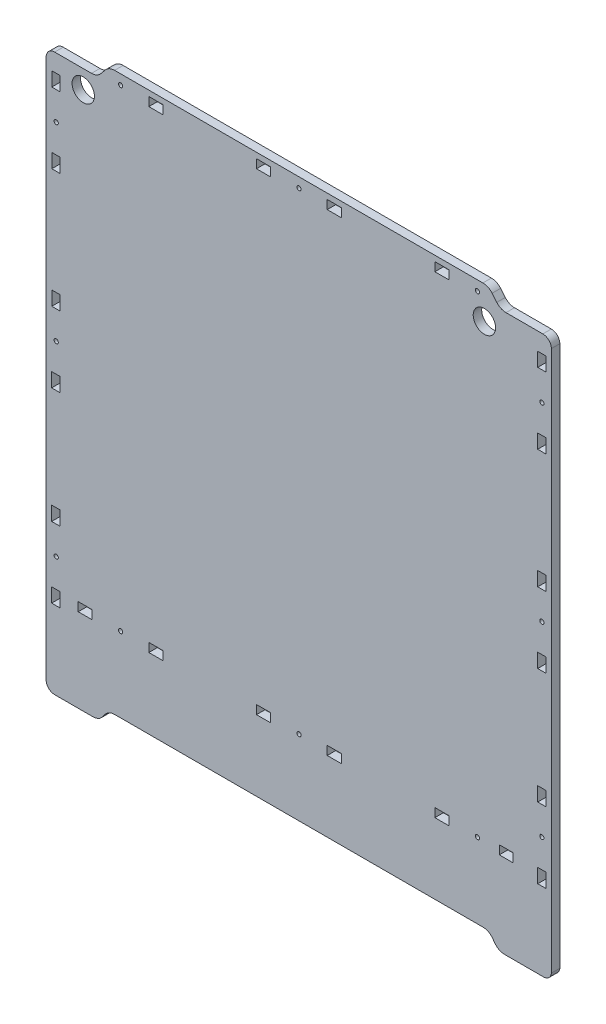
SolidWorks part; units mm, degrees
ref_plane "Спереди" through (0, 0, 0) normal (0, 0, 1) x (1, 0, 0)
ref_plane "Сверху" through (0, 0, 0) normal (0, 1, 0) x (1, 0, 0)
ref_plane "Справа" through (0, 0, 0) normal (1, 0, 0) x (0, 0, -1)
sketch "Эскиз1" plane through (0, 0, 0) normal (0, 0, 1) x (1, 0, 0)
  line L0 (146.8835, 191.543) -> (172.9199, 191.543)
  line L1 (-168.1958, 44.9452) -> (-168.1958, 34.9452)
  line L2 (175.3199, 34.9452) -> (169.2983, 34.9452)
  line L3 (178.9199, 185.543) -> (178.9199, -196.6758)
  line L4 (-178.0801, 185.543) -> (-178.0801, -195.7677)
  line L5 (172.9199, -201.7677) -> (145.8835, -201.7677)
  line L6 (-138.5324, -198.7314) -> (-136.2365, -195.7117)
  line L7 (-172.0801, -201.7677) -> (-145.0437, -201.7677)
  line L8 (-129.7252, -192.6754) -> (130.5649, -192.6754)
  line L9 (139.3721, -198.7314) -> (137.0763, -195.7117)
  line L10 (175.3102, 179.1167) -> (175.3199, 169.3434)
  line L11 (96.6207, 197.6263) -> (106.4199, 197.6434)
  line L12 (106.4199, 197.6434) -> (106.6207, 197.6263)
  line L13 (175.3199, 169.3434) -> (175.3102, 169.2673)
  line L14 (137.0763, 198.5071) -> (140.3721, 194.5793)
  line L15 (130.5649, 201.5434) -> (-129.7252, 201.5434)
  line L16 (-136.2365, 198.5071) -> (-139.5324, 194.5793)
  line L17 (-146.0437, 191.543) -> (-172.0801, 191.543)
  line L18 (106.4199, 191.4434) -> (96.6207, 191.4265)
  line L19 (-168.1958, 34.9452) -> (-174.1022, 34.9452)
  line L20 (30.5209, -142.6754) -> (20.5466, -142.6754)
  line L21 (169.2983, 34.9452) -> (169.2983, 44.9452)
  line L22 (30.5209, -136.4756) -> (30.5209, -142.6754)
  line L23 (-29.4488, -136.4756) -> (-19.4791, -136.4756)
  line L24 (20.5466, -142.6754) -> (20.5466, -136.4756)
  line L25 (-19.4791, -142.6754) -> (-29.4488, -142.6754)
  line L26 (-19.4791, -136.4756) -> (-19.4791, -142.6754)
  line L27 (-168.1958, 179.1167) -> (-168.1958, 169.1167)
  line L28 (-29.4488, -142.6754) -> (-29.4488, -136.4756)
  line L29 (-174.1022, 34.9452) -> (-174.1022, 44.9452)
  line L30 (-174.1022, 44.9452) -> (-168.1958, 44.9452)
  line L31 (20.5466, -136.4756) -> (30.5209, -136.4756)
  line L32 (-174.1022, 179.1167) -> (-168.1958, 179.1167)
  line L33 (106.6155, -142.6768) -> (96.6207, -142.6768)
  line L34 (96.6207, -142.6768) -> (96.6207, -136.477)
  line L35 (96.6207, -136.477) -> (106.6155, -136.477)
  line L36 (106.6155, -136.477) -> (106.6155, -142.6768)
  line L37 (152.0021, -142.6768) -> (142.1529, -142.6768)
  line L38 (142.1529, -142.6768) -> (142.1529, -136.477)
  line L39 (142.1529, -136.477) -> (152.0021, -136.477)
  line L40 (152.0021, -136.477) -> (152.0021, -142.6768)
  line L41 (-19.477, 191.4289) -> (-29.4488, 191.4289)
  line L42 (-29.4488, 191.4289) -> (-29.4488, 197.6287)
  line L43 (-29.4488, 197.6287) -> (-19.477, 197.6287)
  line L44 (-19.477, 197.6287) -> (-19.477, 191.4289)
  line L45 (-174.1022, 119.1168) -> (-174.1022, 129.1168)
  line L46 (-145.5736, -136.477) -> (-145.5736, -142.6768)
  line L47 (-155.4227, -136.477) -> (-145.5736, -136.477)
  line L48 (20.5466, 197.6287) -> (30.523, 197.6287)
  line L49 (30.523, 197.6287) -> (30.523, 191.4289)
  line L50 (-145.5736, -142.6768) -> (-155.4227, -142.6768)
  line L51 (-174.1958, -5.0549) -> (-168.1958, -5.0549)
  line L52 (-174.1958, -15.0549) -> (-174.1958, -5.0549)
  line L53 (-174.1022, 169.1167) -> (-174.1022, 179.1167)
  line L54 (-168.1958, -5.0549) -> (-168.1958, -15.0549)
  line L55 (30.523, 191.4289) -> (20.5466, 191.4289)
  line L56 (-155.4227, -142.6768) -> (-155.4227, -136.477)
  line L57 (-168.1958, 119.1168) -> (-174.1022, 119.1168)
  line L58 (-168.1958, -15.0549) -> (-174.1958, -15.0549)
  line L59 (20.5466, 191.4289) -> (20.5466, 197.6287)
  line L60 (-168.1958, 169.1167) -> (-174.1022, 169.1167)
  line L61 (-174.1958, -86.776) -> (-168.1958, -86.776)
  line L62 (-174.1958, -96.776) -> (-174.1958, -86.776)
  line L63 (-168.1958, 129.1168) -> (-168.1958, 119.1168)
  line L64 (-174.1022, 129.1168) -> (-168.1958, 129.1168)
  line L65 (-174.1958, -136.776) -> (-168.1958, -136.776)
  line L66 (-174.1958, -146.776) -> (-174.1958, -136.776)
  line L67 (-105.5235, -142.6768) -> (-105.5235, -136.477)
  line L68 (-105.5235, -136.477) -> (-95.5735, -136.477)
  line L69 (-95.5735, -136.477) -> (-95.5735, -142.6768)
  line L70 (-168.1958, -146.776) -> (-174.1958, -146.776)
  line L71 (-168.1958, -136.776) -> (-168.1958, -146.776)
  line L72 (-168.1958, -96.776) -> (-174.1958, -96.776)
  line L73 (-168.1958, -86.776) -> (-168.1958, -96.776)
  line L74 (175.3199, -15.0549) -> (169.2983, -15.0549)
  line L75 (169.2983, -96.776) -> (169.2983, -86.776)
  line L76 (175.3199, -5.0549) -> (175.3199, -15.0549)
  line L77 (175.3199, -86.776) -> (175.3199, -96.776)
  line L78 (175.3199, -96.776) -> (169.2983, -96.776)
  line L79 (169.2983, -146.776) -> (169.2983, -136.776)
  line L80 (169.2983, -136.776) -> (175.3199, -136.776)
  line L81 (175.3199, -136.776) -> (175.3199, -146.776)
  line L82 (169.2983, -86.776) -> (175.3199, -86.776)
  line L83 (169.2983, 179.1167) -> (175.3102, 179.1167)
  line L84 (169.2983, 119.1168) -> (169.2983, 129.1168)
  line L85 (169.2983, 129.1168) -> (175.3102, 129.1168)
  line L86 (175.3102, 129.1168) -> (175.3102, 119.1168)
  line L87 (169.2983, 44.9452) -> (175.3199, 44.9452)
  line L88 (175.3102, 169.2673) -> (169.2983, 169.2673)
  line L89 (175.3199, 44.9452) -> (175.3199, 34.9452)
  line L90 (-95.5504, 191.4265) -> (-105.5235, 191.4265)
  line L91 (106.6207, 191.4265) -> (106.4199, 191.4434)
  line L92 (-105.5235, 191.4265) -> (-105.5235, 197.6263)
  line L93 (175.3102, 119.1168) -> (169.2983, 119.1168)
  line L94 (-105.5235, 197.6263) -> (-95.5504, 197.6263)
  line L95 (-95.5504, 197.6263) -> (-95.5504, 191.4265)
  line L96 (175.3199, -146.776) -> (169.2983, -146.776)
  line L97 (169.2983, 169.2673) -> (169.2983, 179.1167)
  line L98 (106.6207, 197.6263) -> (106.6207, 191.4265)
  line L99 (-95.5735, -142.6768) -> (-105.5235, -142.6768)
  line L100 (96.6207, 191.4265) -> (96.6207, 197.6263)
  line L101 (169.2983, -15.0549) -> (169.2983, -5.0549)
  line L102 (169.2983, -5.0549) -> (175.3199, -5.0549)
  arc A0 (-172.0801, 191.543) -> (-178.0801, 185.543) centre (-172.0801, 185.543) ccw
  circle A1 centre (126.6857, -139.5423) radius 1.5
  circle A2 centre (0.6186, -139.5423) radius 1.5
  circle A3 centre (-125.5067, -139.5423) radius 1.5
  arc A4 (172.9199, -201.7677) -> (178.9199, -196.6758) centre (173.3739, -196.2218) ccw
  arc A5 (-129.7252, -192.6754) -> (-136.2365, -195.7117) centre (-129.7252, -201.1754) ccw
  arc A6 (139.3721, -198.7314) -> (145.8835, -201.7677) centre (145.8835, -193.2677) ccw
  arc A7 (-145.0437, -201.7677) -> (-138.5324, -198.7314) centre (-145.0437, -193.2677) ccw
  arc A8 (-178.0801, -195.7677) -> (-172.0801, -201.7677) centre (-172.0801, -195.7677) ccw
  arc A9 (137.0763, -195.7117) -> (130.5649, -192.6754) centre (130.5649, -201.1754) ccw
  arc A10 (178.9199, 185.543) -> (172.9199, 191.543) centre (172.9199, 185.543) ccw
  arc A11 (137.0763, 198.5071) -> (130.5649, 201.5434) centre (130.5649, 193.0434) ccw
  arc A12 (140.3721, 194.5793) -> (146.8835, 191.543) centre (146.8835, 200.043) ccw
  circle A13 centre (-170.9986, -116.6888) radius 1.5
  circle A14 centre (-170.9986, 15.0971) radius 1.5
  circle A15 centre (172.2306, 149.1978) radius 1.5
  circle A16 centre (126.705, 194.5806) radius 1.5
  circle A17 centre (-151.8801, 178.5434) radius 7.9
  circle A18 centre (172.2306, -116.6888) radius 1.5
  circle A19 centre (172.2306, 15.0329) radius 1.5
  circle A20 centre (-170.9986, 149.1705) radius 1.5
  circle A21 centre (-125.4678, 194.5806) radius 1.5
  circle A22 centre (0.6009, 194.5806) radius 1.5
  circle A23 centre (131.6199, 178.5434) radius 7.9
  arc A24 (-129.7252, 201.5434) -> (-136.2365, 198.5071) centre (-129.7252, 193.0434) ccw
  arc A25 (-146.0437, 191.543) -> (-139.5324, 194.5793) centre (-146.0437, 200.043) ccw
extrude "Бобышка-Вытянуть1" add sketch "Эскиз1" along normal blind 6
